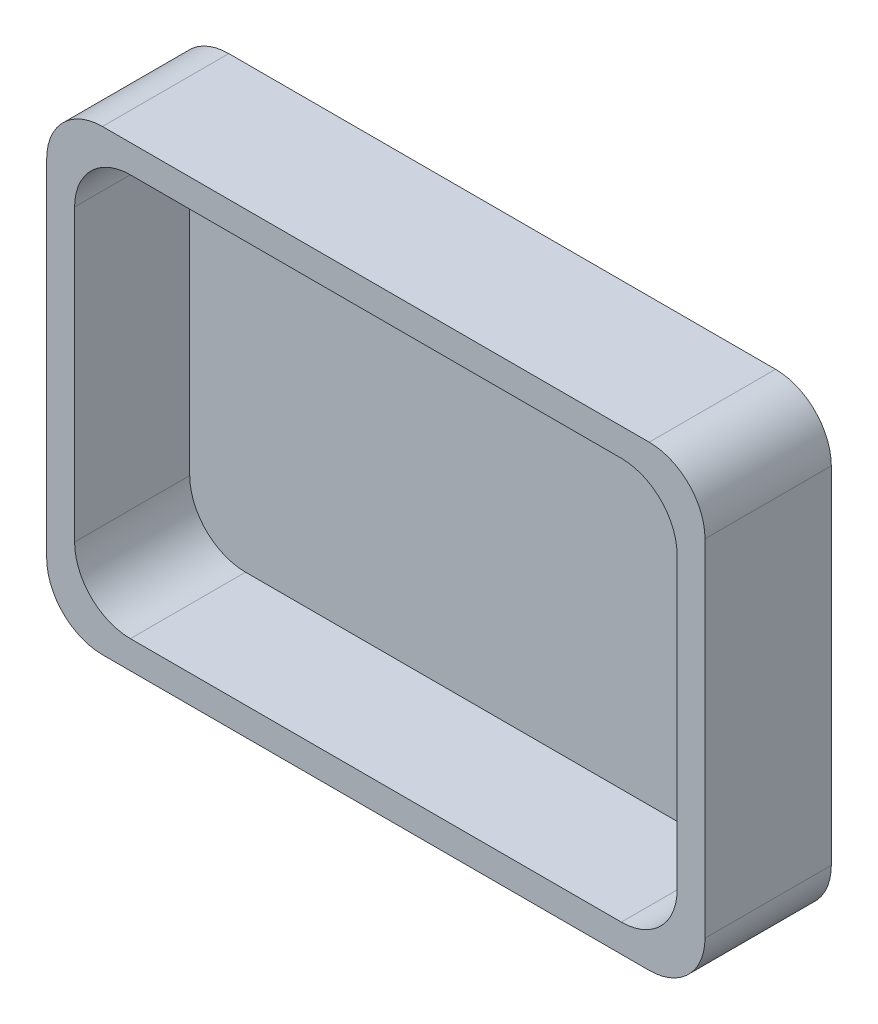
SolidWorks part; units mm, degrees
material "Custom Plastic"
ref_plane "X-Y Datum" through (0, 0, 0) normal (0, 0, 1) x (1, 0, 0)
ref_plane "X-Z Datum" through (0, 0, 0) normal (0, 1, 0) x (1, 0, 0)
ref_plane "Y-Z Datum" through (0, 0, 0) normal (1, 0, 0) x (0, 0, -1)
sketch "Sketch2" plane through (0, 0, 0) normal (0, 0, 1) x (1, 0, 0)
  line L1 (-54, 36) -> (54, 36)
  line L2 (-54, 36) -> (-54, -36)
  line L3 (-54, -36) -> (54, -36)
  line L4 (54, 36) -> (54, -36)
  line L5 (-54, 36) -> (54, -36) construction
  line L6 (-54, -36) -> (54, 36) construction
  point P0 (0, 0)
  dimension "D1" = 72
  dimension "D2" = 108
extrude "Boss-Extrude1" add sketch "Sketch2" along normal blind 20.64
shell "Shell1" thickness 5 removed face at (0, 0, 20.64) outward yes
fillet "Fillet1" radius 10 8 edges at (59, 41, 7.82) (-59, 41, 7.82) (-59, -41, 7.82) (59, -41, 7.82) (54, -36, 10.32) (-54, -36, 10.32) (54, 36, 10.32) (-54, 36, 10.32)
sketch "Sketch3" plane through (0, 0, -5) normal (0, 0, -1) x (-1, 0, 0)
  line L4 (49, 41) -> (-49, 41)
  line L5 (-59, 31) -> (-59, -31)
  line L6 (-49, -41) -> (49, -41)
  line L7 (59, -31) -> (59, 31)
  line L8 (49, 41) -> (-49, 41)
  line L9 (-59, 31) -> (-59, -31)
  line L10 (-49, -41) -> (49, -41)
  line L11 (59, -31) -> (59, 31)
  arc A4 (-49, 41) -> (-59, 31) centre (-49, 31) ccw
  arc A5 (-59, -31) -> (-49, -41) centre (-49, -31) ccw
  arc A6 (49, -41) -> (59, -31) centre (49, -31) ccw
  arc A7 (59, 31) -> (49, 41) centre (49, 31) ccw
  arc A8 (-49, 41) -> (-59, 31) centre (-49, 31) ccw
  arc A9 (-59, -31) -> (-49, -41) centre (-49, -31) ccw
  arc A10 (49, -41) -> (59, -31) centre (49, -31) ccw
  arc A11 (59, 31) -> (49, 41) centre (49, 31) ccw
  dimension "D1" = 0
extrude "Cut-Extrude1" cut sketch "Sketch3" against normal blind 3
